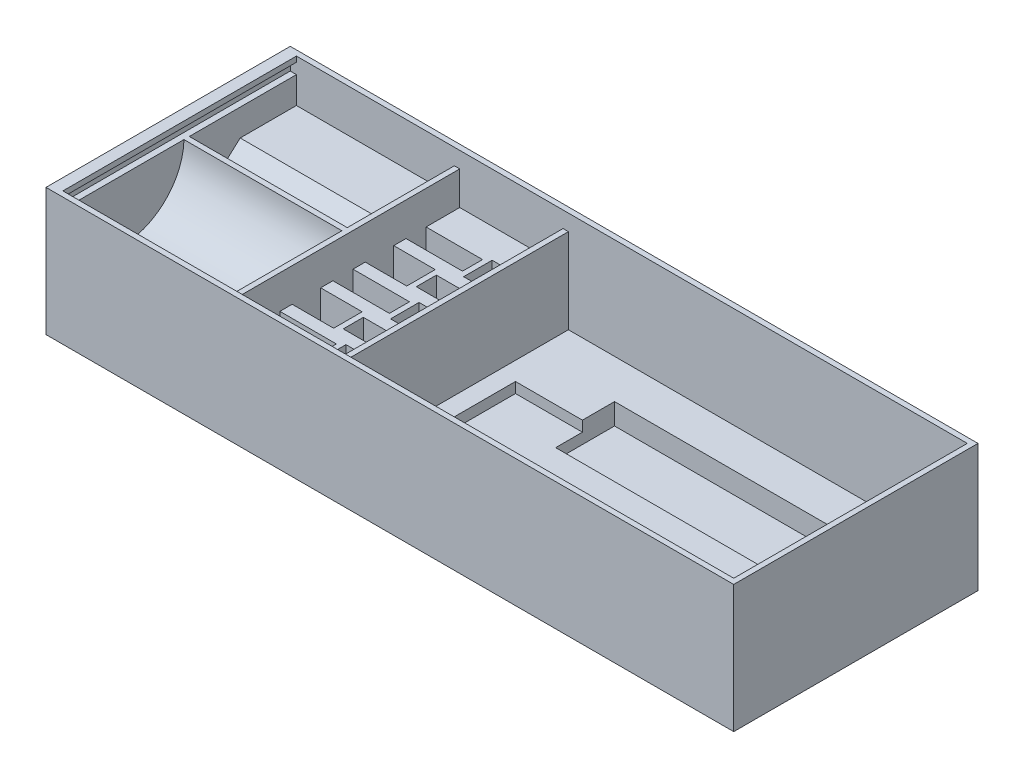
SolidWorks part; units mm, degrees
ref_plane "Front Plane" through (0, 0, 0) normal (0, 0, 1) x (1, 0, 0)
ref_plane "Top Plane" through (0, 0, 0) normal (0, 1, 0) x (1, 0, 0)
ref_plane "Right Plane" through (0, 0, 0) normal (1, 0, 0) x (0, 0, -1)
sketch "Sketch2" plane through (0, 0, 0) normal (0, 0, 1) x (1, 0, 0)
  line L0 (0, 0) -> (0, 41.64)
  line L1 (0, 41.64) -> (-2, 41.64)
  line L2 (-2, 41.64) -> (-2, 9.9)
  line L3 (-2, 9.9) -> (-8.85, 9.9)
  line L4 (-8.85, 9.9) -> (-8.85, 2)
  line L5 (-8.85, 2) -> (-144.15, 2)
  line L6 (-144.15, 2) -> (-144.15, 9.9)
  line L7 (-144.15, 9.9) -> (-151, 9.9)
  line L8 (-151, 9.9) -> (-151, 41.64)
  line L9 (-151, 41.64) -> (-153, 41.64)
  line L10 (-153, 41.64) -> (-191.6, 41.64)
  line L11 (-191.6, 41.64) -> (-193.6, 41.64)
  line L12 (-193.6, 41.64) -> (-193.6, 2)
  line L13 (-193.6, 2) -> (-252.6, 2)
  line L14 (-252.6, 2) -> (-252.6, 41.64)
  line L15 (-252.6, 41.64) -> (-254.9, 41.64)
  line L16 (-254.9, 41.64) -> (-254.9, 45.64)
  line L17 (-254.9, 45.64) -> (-252.6, 45.64)
  line L18 (-252.6, 45.64) -> (-252.6, 47.64)
  line L19 (-252.6, 47.64) -> (-256.9, 47.64)
  line L20 (-256.9, 47.64) -> (-256.9, 0)
  line L21 (-256.9, 0) -> (0, 0)
  line L22 (-252.6, 41.64) -> (-193.6, 41.64)
  line L23 (-151, 41.64) -> (-2, 41.64)
  dimension "D1" = 2
  dimension "D2" = 135.3
  dimension "D3" = 2
  dimension "D4" = 2
  dimension "D5" = 38.6
  dimension "D6" = 59
  dimension "D7" = 252.9
  dimension "D8" = 2
  dimension "D9" = 149
  dimension "D10" = 2
  dimension "D11" = 7.9
  dimension "D12" = 4
  dimension "D13" = 31.74
  dimension "D14" = 2
  dimension "D15" = 2
extrude "Boss-Extrude1" add sketch "Sketch2" against normal blind 2 contours L20 L21 L0 L1 L2 L3 L4 L5 L6 L7 L8 L9 L10 L11 L12 L13 L14 L15 L16 L17 L18 L19 | L22 L14 L13 L12 | L23 L8 L7 L6 L5 L4 L3 L2 region at (-160.2522, 17.153, 0) region at (-76.5, 22.1162, 0) region at (-223.1, 21.82, 0)
extrude "Boss-Extrude2" add sketch "Sketch2<3>" along normal blind 87.25 contours L20 L21 L0 L1 L2 L3 L4 L5 L6 L7 L8 L9 L10 L11 L12 L13 L14 L15 L16 L17 L18 L19 region at (-160.2522, 17.153, 0)
sketch "Sketch2<3>" plane through (0, 0, 0) normal (0, 0, 1) x (1, 0, 0) same geometry as "Sketch2"
sketch "Sketch4" plane through (0, 0, 87.25) normal (0, 0, 1) x (1, 0, 0)
  line L0 (-256.9, 47.64) -> (-256.9, 0) construction
  line L1 (-256.9, 41.64) -> (0, 41.64)
  line L2 (-256.9, 41.64) -> (-256.9, 0)
  line L3 (-256.9, 0) -> (0, 0)
  line L4 (0, 41.64) -> (0, 0)
  line L5 (-256.9, 41.64) -> (-256.9, 47.64)
  line L6 (-256.9, 47.64) -> (-252.6, 47.64)
  line L7 (-252.6, 47.64) -> (-252.6, 45.64)
  line L8 (-252.6, 45.64) -> (-254.9, 45.64)
  line L9 (-254.9, 45.64) -> (-254.9, 41.64)
  line M5 (-256.9, 47.64) -> (-256.9, 0)
  line M6 (-256.9, 0) -> (0, 0)
  line M7 (0, 0) -> (0, 41.64)
  line M8 (0, 41.64) -> (-2, 41.64)
  line M9 (-2, 41.64) -> (-2, 9.9)
  line M10 (-2, 9.9) -> (-8.85, 9.9)
  line M11 (-8.85, 9.9) -> (-8.85, 2)
  line M12 (-8.85, 2) -> (-144.15, 2)
  line M13 (-144.15, 2) -> (-144.15, 9.9)
  line M14 (-144.15, 9.9) -> (-151, 9.9)
  line M15 (-151, 9.9) -> (-151, 41.64)
  line M16 (-151, 41.64) -> (-193.6, 41.64)
  line M17 (-193.6, 41.64) -> (-193.6, 2)
  line M18 (-193.6, 2) -> (-252.6, 2)
  line M19 (-252.6, 2) -> (-252.6, 41.64)
  line M20 (-252.6, 41.64) -> (-254.9, 41.64)
  line M21 (-254.9, 41.64) -> (-254.9, 45.64)
  line M22 (-254.9, 45.64) -> (-252.6, 45.64)
  line M23 (-252.6, 45.64) -> (-252.6, 47.64)
  line M24 (-252.6, 47.64) -> (-256.9, 47.64)
extrude "Boss-Extrude4" add sketch "Sketch4" along normal blind 2 contours L1 M5 M21 M22 M23 M24 | L1 M19 M18 M17 | L1 M5 M6 M7 M8 M9 M10 M11 M12 M13 M14 M15 M16 M17 M18 M19 M20 | L1 M15 M14 M13 M12 M11 M10 M9 region at (-255.3042, 45.1942, 87.25) region at (-159.6359, 16.9712, 87.25) region at (-223.1, 21.82, 87.25) region at (-76.5, 22.1162, 87.25)
sketch "Sketch5" plane through (-252.6, 0, 0) normal (1, 0, 0) x (0, 0, -1)
  line L0 (0, 41.64) -> (0, 31.64)
  line L1 (0, 41.64) -> (-87.25, 41.64)
  line L2 (0, 41.64) -> (0, 2)
  line L3 (0, 2) -> (-87.25, 2)
  line L4 (-87.25, 41.64) -> (-87.25, 2)
  line L5 (0, 31.64) -> (-10, 31.64)
  line L6 (-10, 31.64) -> (-21.0142, 31.64)
  line L7 (-21.0142, 31.64) -> (-53.69, 2)
  line L8 (-53.69, 2) -> (-72.69, 2)
  line L9 (-72.69, 2) -> (-40.0142, 31.64)
  line L10 (-40.0142, 31.64) -> (-42.0142, 31.64)
  line L11 (-42.0142, 31.64) -> (-56.2082, 18.7648)
  line L12 (-56.2082, 18.7648) -> (-87.25, 18.7648)
  line L13 (-40.0142, 31.64) -> (-21.0142, 31.64)
  line L14 (-72.69, 2) -> (-53.69, 2)
  line L16 (-87.25, 2) -> (0, 2) construction
  line L18 (-42.0142, 31.64) -> (-40.0142, 31.64)
  line L19 (-42.0142, 31.64) -> (-42.0142, 41.64)
  line L20 (-42.0142, 41.64) -> (-40.0142, 41.64)
  line L21 (-40.0142, 31.64) -> (-40.0142, 41.64)
  line M13 (0, 2) -> (0, 41.64)
  line M16 (-87.25, 2) -> (0, 2)
  dimension "D1" = 10
  dimension "D2" = 10
  dimension "D3" = 19
  dimension "D4" = 43.69
  dimension "D5" = 19
  dimension "D6" = 42.211
  dimension "D7" = 2
extrude "Boss-Extrude5" add sketch "Sketch5" along normal blind 59 contours L11 L12 L4 L9 L10 M16 | L6 L7 L3 L5 M13 region at (-252.6, 14.6592, 19.8671) region at (-252.6, 12.2999, 73.1366)
extrude "Boss-Extrude6" add sketch "Sketch5<3>" along normal blind 59 contours L10 L21 L1 L19 region at (-252.6, 36.64, 41.0142)
sketch "Sketch5<3>" plane through (-252.6, 0, 0) normal (1, 0, 0) x (0, 0, -1) same geometry as "Sketch5"
sketch "Sketch6" plane through (-252.6, 0, 0) normal (1, 0, 0) x (0, 0, -1)
  line L0 (-87.25, 18.7648) -> (-65.286, 18.7648)
  line L1 (-56.2082, 18.7648) -> (-87.25, 18.7648) construction
  line L5 (-42.0142, 41.64) -> (-42.0142, 31.64)
  line L6 (-42.0142, 31.64) -> (-56.2082, 18.7648)
  line L7 (-56.2082, 18.7648) -> (-65.286, 18.7648)
  arc A0 (-65.286, 18.7648) -> (-42.0142, 41.64) centre (-65.286, 42.0399) ccw
  point P10 (-56.2082, 18.7648)
  line M1 (-56.2082, 18.7648) -> (-42.0142, 31.64)
  line M2 (-42.0142, 31.64) -> (-42.0142, 41.64)
  line M5 (-87.25, 18.7648) -> (-56.2082, 18.7648)
extrude "Boss-Extrude7" add sketch "Sketch6" along normal blind 59 contours A0 M5 M1 M2 region at (-252.6, 36.64, 42.3406)
sketch "Sketch7" plane through (0, 41.64, 0) normal (0, 1, 0) x (1, 0, 0)
  line L0 (0, -89.25) -> (0, 2)
  line L1 (0, 2) -> (-254.9, 2)
  line L3 (-254.9, -89.25) -> (0, -89.25)
  line L4 (-2, -87.25) -> (-2, 0)
  line L5 (-2, 0) -> (-252.6, 0)
  line L7 (-252.6, -87.25) -> (-2, -87.25)
  line L9 (-252.6, -87.25) -> (-254.9, -87.25)
  line L10 (-254.9, 2) -> (-254.9, -89.25) construction
  line L11 (-254.9, -87.25) -> (-254.9, -89.25)
  line L12 (-252.6, 0) -> (-254.9, 0)
  line L13 (-254.9, 0) -> (-254.9, 2)
  point P21 (-254.9, 0)
extrude "Boss-Extrude8" add sketch "Sketch7" along normal blind 6
sketch "Sketch8" plane through (0, 41.64, 0) normal (0, 1, 0) x (1, 0, 0)
  line L1 (-193.6, -87.25) -> (-151, -87.25)
  line L2 (-193.6, -87.25) -> (-193.6, 0)
  line L3 (-193.6, 0) -> (-151, 0)
  line L4 (-151, -87.25) -> (-151, 0)
  line L5 (-191.6, 0) -> (-153, 0)
  line L6 (-191.6, 0) -> (-191.6, -87.25)
  line L7 (-191.6, -87.25) -> (-153, -87.25)
  line L8 (-153, 0) -> (-153, -87.25)
  dimension "D1" = 38.6
  dimension "D2" = 2
extrude "Cut-Extrude1" cut sketch "Sketch8" against normal blind 12.5 contours L6 L5 L8 L7
sketch "Sketch9" plane through (0, 29.14, 0) normal (0, 1, 0) x (1, 0, 0)
  line L0 (-153, 0) -> (-153, -87.25) construction
  line L1 (-191.6, -12.575) -> (-170.5, -12.575)
  line L2 (-191.6, -12.575) -> (-191.6, -20.075)
  line L3 (-191.6, -20.075) -> (-170.5, -20.075)
  line L4 (-170.5, -12.575) -> (-170.5, -20.075)
  line L5 (-168.5, -11) -> (-153, -11)
  line L6 (-168.5, -11) -> (-168.5, -21.65)
  line L7 (-168.5, -21.65) -> (-153, -21.65)
  line L8 (-153, -11) -> (-153, -21.65)
  line L9 (-168.5, -11) -> (-168.5, 0)
  line L10 (-191.6, 0) -> (-191.6, -87.25) construction
  line L11 (-170.5, -12.575) -> (-168.5, -11)
  line L12 (-170.5, -20.075) -> (-168.5, -21.65)
  line L13 (-191.6, -39.875) -> (-170.5, -39.875)
  line L14 (-191.6, -39.875) -> (-191.6, -47.375)
  line L15 (-191.6, -47.375) -> (-170.5, -47.375)
  line L16 (-170.5, -39.875) -> (-170.5, -47.375)
  line L17 (-168.5, -38.3) -> (-153, -38.3)
  line L18 (-168.5, -38.3) -> (-168.5, -48.95)
  line L19 (-168.5, -48.95) -> (-153, -48.95)
  line L20 (-153, -38.3) -> (-153, -48.95)
  line L21 (-170.5, -39.875) -> (-168.5, -38.3)
  line L22 (-170.5, -47.375) -> (-168.5, -48.95)
  line L23 (-191.6, 0) -> (-153, 0) construction
  line L24 (-168.5, -76.25) -> (-168.5, -87.25)
  line L25 (-191.6, -87.25) -> (-153, -87.25) construction
  line L26 (-191.6, -24.65) -> (-191.6, -35.3)
  line L27 (-176.1, -24.65) -> (-176.1, -35.3)
  line L28 (-174.1, -26.225) -> (-176.1, -24.65)
  line L29 (-176.1, -24.65) -> (-191.6, -24.65)
  line L30 (-174.1, -33.725) -> (-176.1, -35.3)
  line L31 (-176.1, -35.3) -> (-191.6, -35.3)
  line L32 (-174.1, -26.225) -> (-174.1, -33.725)
  line L34 (-153, -53.525) -> (-153, -61.025)
  line L43 (-191.6, -67.175) -> (-170.5, -67.175)
  line L44 (-191.6, -67.175) -> (-191.6, -74.675)
  line L45 (-191.6, -74.675) -> (-170.5, -74.675)
  line L46 (-170.5, -67.175) -> (-170.5, -74.675)
  line L47 (-168.5, -65.6) -> (-153, -65.6)
  line L48 (-168.5, -65.6) -> (-168.5, -76.25)
  line L49 (-168.5, -76.25) -> (-153, -76.25)
  line L50 (-153, -65.6) -> (-153, -76.25)
  line L51 (-170.5, -67.175) -> (-168.5, -65.6)
  line L52 (-170.5, -74.675) -> (-168.5, -76.25)
  line L53 (-174.1, -61.025) -> (-176.1, -62.6)
  line L54 (-153, -26.225) -> (-153, -33.725)
  line L55 (-174.1, -53.525) -> (-176.1, -51.95)
  line L56 (-191.6, -51.95) -> (-191.6, -62.6)
  line L57 (-176.1, -62.6) -> (-191.6, -62.6)
  line L58 (-176.1, -51.95) -> (-176.1, -62.6)
  line L59 (-176.1, -51.95) -> (-191.6, -51.95)
  line L60 (-174.1, -53.525) -> (-174.1, -61.025)
  line L61 (-153, -61.025) -> (-174.1, -61.025)
  line L62 (-153, -53.525) -> (-174.1, -53.525)
  line L63 (-153, -33.725) -> (-174.1, -33.725)
  line L64 (-153, -26.225) -> (-174.1, -26.225)
  point P20 (-160.75, -38.3)
  line M44 (-153, -87.25) -> (-153, 0)
  line M46 (-191.6, 0) -> (-191.6, -87.25)
  dimension "D1" = 15.5
  dimension "D2" = 21.1
  dimension "D3" = 7.5
  dimension "D4" = 2
  dimension "D5" = 10.65
  dimension "D6" = 0
  dimension "D7" = 0
  dimension "D8" = 0
  dimension "D9" = 0
extrude "Cut-Extrude2" cut sketch "Sketch9" against normal blind 13.6 contours L6 L7 L5 M44 | L31 L27 L29 M46 | L18 L19 L17 M44 | L58 L59 L57 M46 | L48 L49 L47 M44 region at (-160.75, 29.14, 16.325) region at (-183.85, 29.14, 29.975) region at (-160.75, 29.14, 43.625) region at (-183.85, 29.14, 57.275) region at (-160.75, 29.14, 70.925)
extrude "Cut-Extrude3" cut sketch "Sketch9<4>" against normal blind 8.6 contours L4 L1 L3 M46 | L64 L32 L63 M44 | L16 L13 L15 M46 | L62 L60 L61 M44 | L46 L43 L45 M46 region at (-181.05, 29.14, 16.325) region at (-181.05, 29.14, 43.625) region at (-163.55, 29.14, 29.975) region at (-181.05, 29.14, 70.925) region at (-163.55, 29.14, 57.275)
sketch "Sketch9<4>" plane through (0, 29.14, 0) normal (0, 1, 0) x (1, 0, 0) same geometry as "Sketch9"
sketch "Sketch10" plane through (0, 2, 0) normal (0, 1, 0) x (1, 0, 0)
  line L0 (-144.15, -87.25) -> (-144.15, 0) construction
  line L1 (-144.15, -36.625) -> (-8.85, -36.625)
  line L2 (-144.15, -36.625) -> (-144.15, -72.625)
  line L3 (-144.15, -72.625) -> (-8.85, -72.625)
  line L4 (-8.85, -36.625) -> (-8.85, -72.625)
  line L5 (-8.85, -87.25) -> (-8.85, 0) construction
  line L6 (-76.5, -14.625) -> (-76.5, 0)
  line L7 (-144.15, -36.625) -> (-8.85, -36.625)
  line L8 (-144.15, -36.625) -> (-144.15, -26.625)
  line L9 (-144.15, -26.625) -> (-8.85, -26.625)
  line L10 (-8.85, -36.625) -> (-8.85, -26.625)
  line L11 (-144.15, -26.625) -> (-8.85, -26.625)
  line L12 (-144.15, -26.625) -> (-144.15, -14.625)
  line L13 (-144.15, -14.625) -> (-8.85, -14.625)
  line L14 (-8.85, -26.625) -> (-8.85, -14.625)
  line L15 (-8.85, 0) -> (-144.15, 0) construction
  line L17 (-76.5, -72.625) -> (-76.5, -87.25)
  line L18 (-8.85, -87.25) -> (-144.15, -87.25) construction
  line M16 (-8.85, 0) -> (-144.15, 0)
  line M17 (-144.15, 0) -> (-144.15, -87.25)
  line M18 (-144.15, -87.25) -> (-8.85, -87.25)
  line M19 (-8.85, -87.25) -> (-8.85, 0)
  dimension "D1" = 36
  dimension "D2" = 10
  dimension "D3" = 12
extrude "Boss-Extrude9" add sketch "Sketch10" along normal blind 7.9 contours L13 L6 M17 M16 | L6 L13 M19 M16 | L3 L17 M18 M19 | L17 L3 M17 M18 region at (-110.325, 2, 79.9375) region at (-42.675, 2, 79.9375) region at (-110.325, 2, 7.3125) region at (-42.675, 2, 7.3125)
extrude "Boss-Extrude10" add sketch "Sketch10<4>" along normal blind 4 contours L3 L1 M17 M19 region at (-76.5, 2, 54.625)
sketch "Sketch10<4>" plane through (0, 2, 0) normal (0, 1, 0) x (1, 0, 0) same geometry as "Sketch10"
sketch "Sketch11" plane through (0, 0, 14.625) normal (0, 0, 1) x (1, 0, 0)
  line L0 (-144.15, 9.9) -> (-8.85, 9.9) construction
  line L1 (-144.15, 2) -> (-119.15, 2)
  line L2 (-144.15, 2) -> (-144.15, 9.9)
  line L3 (-144.15, 9.9) -> (-119.15, 9.9)
  line L4 (-119.15, 2) -> (-119.15, 9.9)
  line L5 (-144.15, 2) -> (-8.85, 2) construction
  line L6 (-8.85, 9.9) -> (-33.85, 9.9)
  line L7 (-8.85, 9.9) -> (-8.85, 2)
  line L8 (-8.85, 2) -> (-33.85, 2)
  line L9 (-33.85, 9.9) -> (-33.85, 2)
  dimension "D1" = 25
extrude "Boss-Extrude14" add sketch "Sketch11" along normal blind 22
sketch "Sketch12" plane through (0, 9.9, 0) normal (0, 1, 0) x (1, 0, 0)
  line L0 (-119.15, -36.625) -> (-119.15, -14.625) construction
  line L1 (-144.15, -36.625) -> (-119.15, -36.625)
  line L2 (-144.15, -36.625) -> (-144.15, -26.625)
  line L3 (-144.15, -26.625) -> (-119.15, -26.625)
  line L4 (-119.15, -36.625) -> (-119.15, -26.625)
  line L5 (-8.85, -72.625) -> (-8.85, -36.625) construction
  line L6 (-33.85, -36.625) -> (-8.85, -36.625)
  line L7 (-33.85, -36.625) -> (-33.85, -26.625)
  line L8 (-33.85, -26.625) -> (-8.85, -26.625)
  line L9 (-8.85, -36.625) -> (-8.85, -26.625)
  dimension "D1" = 10
  dimension "D2" = 10
extrude "Cut-Extrude4" cut sketch "Sketch12" against normal blind 3.9
sketch "Sketch13" plane through (-151, 0, 0) normal (1, 0, 0) x (0, 0, -1)
  line L6 (-89.25, 41.64) -> (2, 41.64)
  line L7 (-89.25, 41.64) -> (-89.25, 0)
  line L8 (-89.25, 0) -> (2, 0)
  line L9 (2, 41.64) -> (2, 0)
  line L11 (-89.25, 41.64) -> (2, 41.64)
  line L12 (-89.25, 41.64) -> (-89.25, 47.64)
  line L13 (-89.25, 47.64) -> (2, 47.64)
  line L14 (2, 41.64) -> (2, 47.64)
  point P6 (-43.625, 41.64)
  dimension "D2" = 91.25
  dimension "D3" = 41.64
  dimension "D4" = 6
equation "\"temp\"=9.84883"
